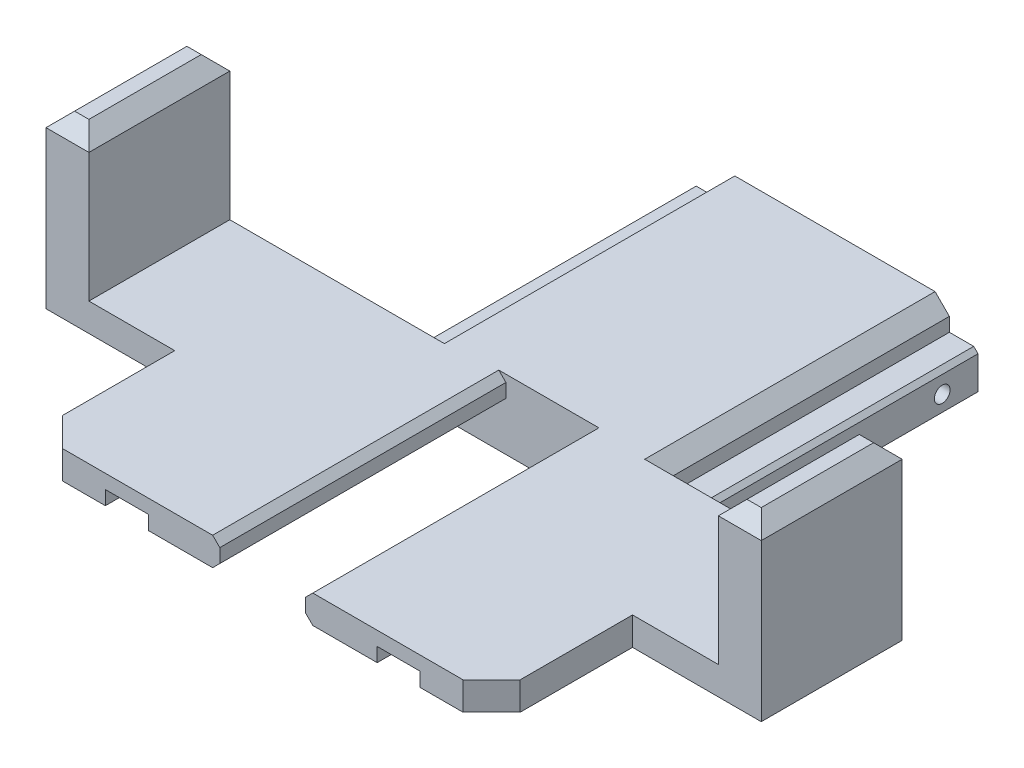
SolidWorks part; units mm, degrees
ref_plane "前视基准面" through (0, 0, 0) normal (0, 0, 1) x (1, 0, 0)
ref_plane "上视基准面" through (0, 0, 0) normal (0, 1, 0) x (1, 0, 0)
ref_plane "右视基准面" through (0, 0, 0) normal (1, 0, 0) x (0, 0, -1)
sketch "草图1" plane through (0, 0, 0) normal (0, 0, 1) x (1, 0, 0)
  line L0 (-10, 0.4853) -> (-8, 0.4853)
  line L1 (-8, 2.45) -> (8, 2.45)
  line L2 (-10, 0.4853) -> (-10, -2.4147)
  line L3 (-10, -2.4147) -> (10, -2.4147)
  line L4 (10, 0.4853) -> (10, -2.4147)
  line L5 (0, 0) -> (0, 2.45) construction
  line L7 (-8, 0.4853) -> (-8, 2.45)
  line L9 (10, 0.4853) -> (8, 0.4853)
  line L10 (8, 0.4853) -> (8, 2.45)
  point P0 (0, 0)
  dimension "D1" = 2
  dimension "D2" = 2
  dimension "D3" = 2.9
  dimension "D4" = 8
  dimension "D5" = 8
extrude "凸台-拉伸1" add sketch "草图1" along normal blind 20
sketch "草图2" plane through (10, 0, 0) normal (1, 0, 0) x (0, 0, -1)
  line L4 (0, -2.4147) -> (0, 0.4853)
  line L5 (0, 0.4853) -> (-20, 0.4853)
  line L6 (-20, 0.4853) -> (-20, -2.4147)
  line L7 (-20, -2.4147) -> (0, -2.4147)
  line L8 (0, -2.4147) -> (0, 0.4853)
  line L9 (0, 0.4853) -> (-20, 0.4853)
  line L10 (-20, 0.4853) -> (-20, -2.4147)
  line L11 (-20, -2.4147) -> (0, -2.4147)
  circle A0 centre (-2.5, -1.0147) radius 0.55
  circle A1 centre (-18.5, -1.0147) radius 0.55
  dimension "D2" = 1.1
  dimension "D3" = 1.5
  dimension "D4" = 1.5
  dimension "D5" = 1.5
  dimension "D6" = 16
  dimension "D1" = 0
extrude "切除-拉伸1" cut sketch "草图2" against normal through all contours A0 | A1
sketch "草图3" plane through (0, 0, 20) normal (0, 0, 1) x (1, 0, 0)
  line L0 (-8, 0.4853) -> (8, 0.4853)
  line L8 (10, -2.4147) -> (10, 0.4853)
  line L9 (10, 0.4853) -> (8, 0.4853)
  line L10 (8, 0.4853) -> (8, 2.45)
  line L11 (8, 2.45) -> (-8, 2.45)
  line L12 (-8, 2.45) -> (-8, 0.4853)
  line L13 (-8, 0.4853) -> (-10, 0.4853)
  line L14 (-10, 0.4853) -> (-10, -2.4147)
  line L15 (-10, -2.4147) -> (10, -2.4147)
  line L18 (8, 0.4853) -> (8, 2.45)
  line L19 (8, 2.45) -> (-8, 2.45)
  line L20 (-8, 2.45) -> (-8, 0.4853)
  dimension "D1" = 0
extrude "凸台-拉伸2" add sketch "草图3" along normal blind 20
sketch "草图4" plane through (0, 0.4853, 0) normal (0, -1, 0) x (1, 0, 0)
  line L0 (-3, 40) -> (-3, 20)
  line L1 (3, 40) -> (3, 20)
  line L4 (-8, 20) -> (8, 20)
  line L5 (8, 20) -> (8, 40)
  line L6 (8, 40) -> (-8, 40)
  line L7 (-8, 40) -> (-8, 20)
  line L8 (-3, 20) -> (3, 20)
  line L10 (3, 40) -> (-3, 40)
  dimension "D2" = 6
  dimension "D1" = 0
extrude "切除-拉伸2" cut sketch "草图4" against normal through all
sketch "草图6" plane through (-8, 0, 0) normal (-1, 0, 0) x (0, 0, 1)
  line L1 (20.3, 0.4853) -> (20.3, 2.45)
  line L5 (0, 2.45) -> (0, 0.4853)
  line L6 (0, 0.4853) -> (20, 0.4853)
  line L7 (20, 0.4853) -> (40, 0.4853)
  line L8 (40, 0.4853) -> (40, 2.45)
  line L9 (40, 2.45) -> (0, 2.45)
  line L12 (20.3, 0.4853) -> (40, 0.4853)
  line L13 (40, 0.4853) -> (40, 2.45)
  line L14 (40, 2.45) -> (20.3, 2.45)
  dimension "D2" = 0.3
  dimension "D1" = 0
extrude "凸台-拉伸13" add sketch "草图6" along normal blind 17
sketch "草图7" plane through (8, 0, 0) normal (1, 0, 0) x (0, 0, -1)
  line L0 (-20.3, 0.4853) -> (-20.3, 2.45)
  line L5 (0, 0.4853) -> (0, 2.45)
  line L6 (0, 2.45) -> (-40, 2.45)
  line L7 (-40, 2.45) -> (-40, 0.4853)
  line L8 (-40, 0.4853) -> (-20, 0.4853)
  line L9 (-20, 0.4853) -> (0, 0.4853)
  line L11 (-20.3, 2.45) -> (-40, 2.45)
  line L12 (-40, 2.45) -> (-40, 0.4853)
  line L13 (-40, 0.4853) -> (-20.3, 0.4853)
  dimension "D2" = 0.3
  dimension "D1" = 0
extrude "凸台-拉伸14" add sketch "草图7" along normal blind 17
sketch "草图8" plane through (0, 2.45, 0) normal (0, 1, 0) x (1, 0, 0)
  line L0 (-22, -20.3) -> (-22, -30.15)
  line L1 (22, -20.3) -> (22, -30.15)
  line L2 (-25, -30.15) -> (-22, -30.15)
  line L3 (25, -30.15) -> (22, -30.15)
  line L12 (-3, -20) -> (3, -20)
  line L13 (3, -20) -> (3, -40)
  line L14 (3, -40) -> (25, -40)
  line L15 (25, -40) -> (25, -20.3)
  line L16 (25, -20.3) -> (8, -20.3)
  line L17 (8, -20.3) -> (8, 0)
  line L18 (8, 0) -> (-8, 0)
  line L19 (-8, 0) -> (-8, -20.3)
  line L20 (-8, -20.3) -> (-25, -20.3)
  line L21 (-25, -20.3) -> (-25, -40)
  line L22 (-25, -40) -> (-3, -40)
  line L23 (-3, -40) -> (-3, -20)
  line L27 (25, -30.15) -> (25, -20.3)
  line L28 (25, -20.3) -> (22, -20.3)
  line L32 (-22, -20.3) -> (-25, -20.3)
  line L33 (-25, -20.3) -> (-25, -30.15)
  dimension "D2" = 3
  dimension "D3" = 3
  dimension "D1" = 0
extrude "凸台-拉伸15" add sketch "草图8" along normal blind 10
chamfer "倒角1" distance 0.3 angle 45 4 edges at (-10, -2.4147, 10) (-10, 0.4853, 10) (10, -2.4147, 10) (10, 0.4853, 10)
sketch "草图10" plane through (0, 0, 20.3) normal (0, 0, -1) x (-1, 0, 0)
  line L0 (-8, 0.4853) -> (-8, 2.45) construction
  line L5 (-25, 0.4853) -> (-8, 0.4853) construction
  line L6 (8, 2.45) -> (8, 0.4853) construction
  line L7 (8, 0.4853) -> (25, 0.4853) construction
  line L12 (-8, 0.4853) -> (-8, 1.4677)
  line L17 (-11, 0.4853) -> (-8, 0.4853)
  line L18 (8, 1.4677) -> (8, 0.4853)
  line L19 (8, 0.4853) -> (11, 0.4853)
  line L24 (8, 1.4677) -> (11, 1.4677)
  line L25 (11, 1.4677) -> (11, 0.4853)
  line L26 (-8, 1.4677) -> (-11, 1.4677)
  line L27 (-11, 1.4677) -> (-11, 0.4853)
  dimension "D1" = 3
  dimension "D2" = 3
extrude "切除-拉伸3" cut sketch "草图10" against normal through all
chamfer "倒角3" distance 0.5 angle 45 4 edges at (-3, 0.4853, 30) (3, 0.4853, 30) (3, 2.45, 30) (-3, 2.45, 30)
chamfer "倒角4" distance 1 angle 45 2 edges at (-8, 2.45, 10.15) (8, 2.45, 10.15)
chamfer "倒角5" distance 1 angle 45 8 edges at (25, 12.45, 25.225) (23.5, 12.45, 30.15) (22, 12.45, 25.225) (23.5, 12.45, 20.3) (-22, 12.45, 25.225) (-23.5, 12.45, 30.15) (-25, 12.45, 25.225) (-23.5, 12.45, 20.3)
sketch "草图11" plane through (0, 2.45, 0) normal (0, 1, 0) x (1, 0, 0)
  line L1 (-25, -30.15) -> (-16, -30.15)
  line L2 (-25, -30.15) -> (-25, -40)
  line L3 (-25, -40) -> (-16, -40)
  line L4 (-16, -30.15) -> (-16, -40)
  line L5 (25, -30.15) -> (16, -30.15)
  line L6 (25, -30.15) -> (25, -40)
  line L7 (25, -40) -> (16, -40)
  line L8 (16, -30.15) -> (16, -40)
  line L16 (7, 0) -> (-7, 0)
  line L17 (-7, 0) -> (-7, -20.3)
  line L18 (-7, -20.3) -> (-22, -20.3)
  line L19 (-22, -20.3) -> (-22, -30.15)
  line L20 (-22, -30.15) -> (-25, -30.15)
  line L21 (-25, -30.15) -> (-25, -40)
  line L22 (-25, -40) -> (-3.5, -40)
  line L23 (-3.5, -40) -> (-3.5, -20)
  line L24 (-3.5, -20) -> (3.5, -20)
  line L25 (3.5, -20) -> (3.5, -40)
  line L26 (3.5, -40) -> (25, -40)
  line L27 (25, -40) -> (25, -30.15)
  line L28 (25, -30.15) -> (22, -30.15)
  line L29 (22, -30.15) -> (22, -20.3)
  line L30 (22, -20.3) -> (7, -20.3)
  line L31 (7, -20.3) -> (7, 0)
  line L36 (-22, -30.15) -> (-25, -30.15)
  line L37 (-25, -30.15) -> (-25, -40)
  line L38 (-25, -40) -> (-16, -40)
  line L42 (16, -40) -> (25, -40)
  line L43 (25, -40) -> (25, -30.15)
  line L44 (25, -30.15) -> (22, -30.15)
  line M25 (-22, -30.15) -> (-25, -30.15)
  line M26 (-25, -30.15) -> (-25, -40)
  line M27 (-25, -40) -> (-3.5, -40)
  line M31 (3.5, -40) -> (25, -40)
  line M32 (25, -40) -> (25, -30.15)
  line M33 (25, -30.15) -> (22, -30.15)
  dimension "D2" = 9
  dimension "D3" = 9
  dimension "D1" = 0
extrude "切除-拉伸4" cut sketch "草图11" against normal through all contours L4 L1 M25 M26 M27 | L5 L8 M31 M32 M33 region at (-20.5, 2.45, 35.075) region at (20.5, 2.45, 35.075)
chamfer "倒角6" distance 2 angle 45 2 edges at (16, 1.4677, 40) (-16, 1.4677, 40)
